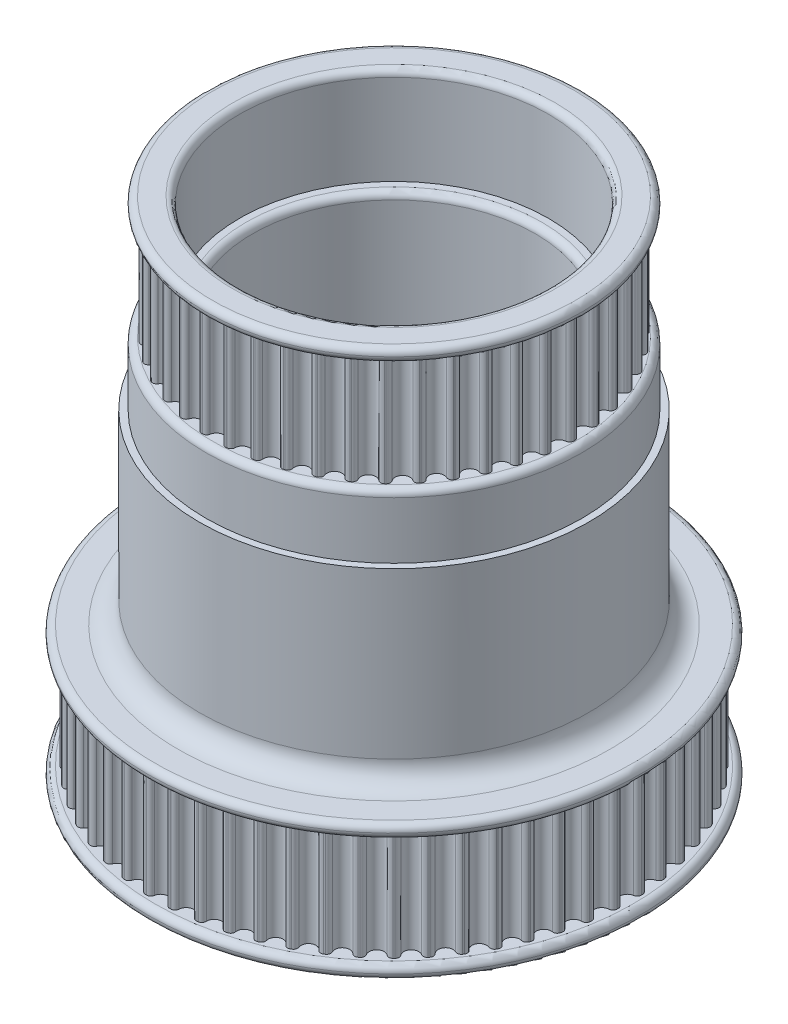
SolidWorks part; units mm, degrees
ref_plane "Front Plane" through (0, 0, 0) normal (0, 0, 1) x (1, 0, 0)
ref_plane "Top Plane" through (0, 0, 0) normal (0, 1, 0) x (1, 0, 0)
ref_plane "Right Plane" through (0, 0, 0) normal (1, 0, 0) x (0, 0, -1)
sketch "PulleyOffsets" plane through (0, 0, 0) normal (1, 0, 0) x (0, 0, -1)
  line L0 (22.225, 0) -> (-22.225, 0) construction
  line L1 (22.225, 44.45) -> (-22.225, 44.45) construction
  line L2 (0, 0) -> (0, 44.45) construction
  point P7 (0, 0)
  dimension "D1" = 44.45
ref_axis "Axis1" through (0, 34.9332, 0) along (0, -1, 0)
ref_plane "Big Pulley Plane" through (0, 0, 0) normal (0, 1, 0) x (1, 0, 0)
ref_plane "Small Pulley Plane" through (0, 44.45, 0) normal (0, 1, 0) x (1, 0, 0)
sketch "Sketch1" plane through (0, 0, 0) normal (0, 1, 0) x (1, 0, 0)
  line L0 (0, 0) -> (0, 28.2667) construction
  line L1 (0, 0) -> (2.9202, 27.7837) construction
  circle A0 centre (0, 0) radius 28.2667 construction
  circle A1 centre (0, 0) radius 27.0467 construction
  circle A2 centre (0, 27.9367) radius 0.89 construction
  circle A5 centre (2.9202, 27.7837) radius 0.89 construction
  arc A6 (0, 27.0467) -> (0.8804, 27.8061) centre (0, 27.9367) ccw
  arc A7 (0.8804, 27.8061) -> (1.3997, 28.2321) centre (1.3749, 27.7327) cw
  arc A8 (1.559, 28.2237) -> (2.031, 27.7458) centre (1.5314, 27.7245) cw
  arc A9 (2.8272, 26.8986) -> (2.031, 27.7458) centre (2.9202, 27.7837) cw
  arc A10 (1.3997, 28.2321) -> (1.559, 28.2237) centre (0, 0) cw
  arc A11 (0, 27.0467) -> (2.8272, 26.8986) centre (0, 0) ccw
  dimension "D1" = 56.5335
  dimension "D3" = 1.78
  dimension "D4" = 0.5
  dimension "D2" = 1.22
  dimension "D5" = 6
extrude "Boss-Extrude1" add sketch "Sketch1" along normal mid plane 13 contours A6 A11 A9 A8 A7 region at (0.001, 0, -0.0192)
pattern_circular "CirPattern1" count 60 over 360 about axis through (0, 34.9332, 0) along (0, -1, 0) of "Boss-Extrude1"
sketch "Sketch2" plane through (0, 0, 0) normal (1, 0, 0) x (0, 0, -1)
  line L10 (0, 6.5) -> (29.4415, 6.5) construction
  line L11 (0, 6.5) -> (0, 8.0875) construction
  line L12 (0, 8.0875) -> (29.4415, 8.0875) construction
  line L15 (29.4415, 6.5) -> (29.4415, 8.0875) construction
  line L20 (0, 34.9332) -> (0, -6.9932) construction
  line L22 (29.4415, 8.0875) -> (0, 8.0875)
  line L23 (29.4415, 8.0875) -> (29.4415, 6.5)
  line L24 (29.4415, 6.5) -> (0, 6.5)
  line L25 (0, 8.0875) -> (0, 6.5)
  dimension "D1" = 1.5875
  dimension "D2" = 29.4415
  dimension "D3" = 6.5
revolve "Revolve3" add sketch "Sketch2" angle 360 about axis through (0, 34.9332, 0) along (0, -1, 0) region at (0, 7.2937, -14.7207)
mirror "Mirror1" about plane through (0, 0, 0) normal (0, 1, 0) of "Revolve3"
sketch "Sketch6" plane through (0, 0, 0) normal (0, 1, 0) x (1, 0, 0)
  line L0 (0, 0) -> (0, 21.582) construction
  line L1 (0, 0) -> (2.8938, 21.0541) construction
  circle A0 centre (0, 0) radius 21.582 construction
  circle A1 centre (0, 0) radius 20.362 construction
  circle A2 centre (0, 21.252) radius 0.89 construction
  circle A5 centre (2.8938, 21.0541) radius 0.89 construction
  arc A6 (0, 20.362) -> (0.8793, 21.1145) centre (0, 21.252) ccw
  arc A7 (0.8793, 21.1145) -> (1.4059, 21.5362) centre (1.3733, 21.0373) cw
  arc A8 (1.5397, 21.527) -> (2.004, 21.0376) centre (1.5041, 21.0283) cw
  arc A9 (2.7726, 20.1724) -> (2.004, 21.0376) centre (2.8938, 21.0541) cw
  arc A10 (1.4059, 21.5362) -> (1.5397, 21.527) centre (0, 0) cw construction
  arc A11 (0, 20.362) -> (2.7726, 20.1724) centre (0, 0) ccw
  arc A12 (1.4059, 21.5362) -> (1.5397, 21.527) centre (0, 0) cw
  dimension "D3" = 1.78
  dimension "D4" = 0.5
  dimension "D2" = 1.22
  dimension "D1" = 43.1641
  dimension "D5" = 7.826
extrude "Boss-Extrude2" add sketch "Sketch6" along normal mid plane 13 from surface contours A6 A11 A9 A8 A7 region at (0.0017, 0, -0.025) starting at plane "Small Pulley Plane"
pattern_circular "CirPattern2" count 46 over 360 about axis through (0, 34.9332, 0) along (0, -1, 0) of "Boss-Extrude2"
sketch "Sketch9" plane through (0, 0, 0) normal (1, 0, 0) x (0, 0, -1)
  line L1 (0, 37.95) -> (22.7568, 37.95)
  line L2 (0, 37.95) -> (0, 36.3625)
  line L3 (0, 36.3625) -> (22.7568, 36.3625)
  line L4 (22.7568, 37.95) -> (22.7568, 36.3625)
  line L6 (0, 50.95) -> (22.7568, 50.95)
  line L7 (0, 50.95) -> (0, 52.5375)
  line L8 (0, 52.5375) -> (22.7568, 52.5375)
  line L9 (22.7568, 50.95) -> (22.7568, 52.5375)
  line L10 (29.4415, 8.0875) -> (29.4415, 6.5) construction
  line L11 (0, 34.9332) -> (0, -6.9932) construction
  line L12 (21.1145, 50.95) -> (20.362, 50.95) construction
  line L13 (20.1641, 37.95) -> (21.0376, 37.95) construction
  dimension "D1" = 22.7568
revolve "Revolve4" add sketch "Sketch9" angle 360 about axis through (0, 34.9332, 0) along (0, -1, 0)
sketch "Sketch10" plane through (0, -8.0875, 0) normal (0, -1, 0) x (1, 0, 0)
  circle A0 centre (0, 0) radius 18.5
  dimension "D1" = 37
extrude "Cut-Extrude1" cut sketch "Sketch10" against normal through all
sketch "Sketch11" plane through (0, 52.5375, 0) normal (0, 1, 0) x (1, 0, 0)
  circle A0 centre (0, 0) radius 22.5
  dimension "D1" = 45
extrude "Cut-Extrude2" cut sketch "Sketch11" against normal up to surface (16.175 mm away) flip side to cut up to face at (0, 36.3625, 18.5)
sketch "Sketch12" plane through (0, 0, 0) normal (0, 0, 1) x (1, 0, 0)
  line L0 (29.4415, 8.0875) -> (-29.4415, 8.0875) construction
  line L1 (18.5, 36.3625) -> (22.5, 36.3625)
  line L2 (18.5, 36.3625) -> (18.5, 8.0875) construction
  line L3 (18.5, 8.0875) -> (22.5, 8.0875)
  line L4 (22.5, 36.3625) -> (22.5, 8.0875) construction
  line L5 (22.5, 36.3625) -> (22.5, 37.95) construction
  line L6 (22.5, 30.3625) -> (22.5, 36.3625)
  line L7 (22.5, 30.3625) -> (23.2938, 30.3625)
  line L8 (22.5, 30.3625) -> (22.5, 8.0875) construction
  line L9 (22.5, 8.0875) -> (23.2938, 8.0875)
  line L10 (23.2938, 30.3625) -> (23.2938, 8.0875)
  line L11 (18.5, -8.0875) -> (18.5, 8.0875) construction
  line L12 (18.5, 2.0875) -> (16.9125, 2.0875)
  line L13 (18.5, 2.0875) -> (18.5, 40.95) construction
  line L14 (18.5, 40.95) -> (16.9125, 40.95)
  line L15 (16.9125, 2.0875) -> (16.9125, 40.95)
  line L16 (-29.4415, -8.0875) -> (29.4415, -8.0875) construction
  line L18 (18.5, 2.0875) -> (18.5, 8.0875)
  line L19 (18.5, 36.3625) -> (18.5, 40.95)
  line L20 (32.3856, 44.45) -> (-32.3856, 44.45) construction
  dimension "D1" = 6
  dimension "D2" = 0.7937
  dimension "D3" = 10.175
  dimension "D5" = 1.5875
  dimension "D4" = 3.5
revolve "Revolve5" add sketch "Sketch12" angle 360 about axis through (0, 34.9332, 0) along (0, -1, 0)
fillet "Fillet1" radius 2.54 1 edges at (0, 8.0875, -23.2938)
fillet "Fillet2" radius 0.7937 11 edges at (0, 40.95, 16.9125) (0, 52.5375, -18.5) (0, -8.0875, -18.5) (0, 2.0875, 16.9125) (0, -8.0875, 29.4415) (0, 8.0875, 29.4415) (0, 52.5375, 22.5) (0, 50.95, 22.5) (0, 37.95, -22.5) (0, 6.5, 29.4415) (0, -6.5, 29.4415)
equation "\"TEETH_NUM\"= 60"
equation "\"TOOTH_PITCH\"= 3mm"
equation "\"PITCH_LINE_OFFSET\"= .015in"
equation "\"DIAMETER_PER_GROOVE\"= \"OUTSIDE_DIAMETER\" / \"TEETH_NUM\" * 1in"
equation "\"PITCH_DIAMETER\"= ( ( \"TEETH_NUM\" * 3 - 1.31 ) / 3.1415 + .415 ) * 1mm"
equation "\"OUTSIDE_DIAMETER\"= \"PITCH_DIAMETER\" - \"PITCH_LINE_OFFSET\" * 2"
equation "\"D1@Sketch1\"=\"OUTSIDE_DIAMETER\""
equation "\"TOOTH_HEIGHT\"= 1.22mm"
equation "\"D2@Sketch1\"=\"TOOTH_HEIGHT\""
equation "\"TOOTH_DIAMETER\"= 1.78mm"
equation "\"INTERNAL_RADIUS\"= .5mm"
equation "\"D3@Sketch1\"=\"TOOTH_DIAMETER\""
equation "\"D5@Sketch1\"=360 / \"TEETH_NUM\""
equation "\"D4@Sketch1\"=\"INTERNAL_RADIUS\""
equation "\"D1@CirPattern1\"=\"TEETH_NUM\""
equation "\"BELT_GAP\"= 13mm"
equation "\"D2@Sketch2\"=\"PITCH_DIAMETER\"/2+1/32"
equation "\"D3@Sketch2\"=\"BELT_GAP\"/2"
equation "\"2_TEETH_NUM\"= 46"
equation "\"2_PITCH_DIAMETER\"= ( ( \"2_TEETH_NUM\" * 3 - 1.31 ) / 3.1415 + .415 ) * 1mm"
equation "\"2_OUTSIDE_DIAMETER\"= \"2_PITCH_DIAMETER\" - \"PITCH_LINE_OFFSET\" * 2"
equation "\"2_DIAMETER_PER_GROOVE\"= \"2_OUTSIDE_DIAMETER\" / \"2_TEETH_NUM\" * 1in"
equation "\"D5@Sketch6\"=360/\"2_TEETH_NUM\""
equation "\"D1@Sketch6\"=\"2_OUTSIDE_DIAMETER\""
equation "\"D2@Sketch6\"=\"TOOTH_HEIGHT\""
equation "\"D3@Sketch6\"=\"TOOTH_DIAMETER\""
equation "\"D4@Sketch6\"=\"INTERNAL_RADIUS\""
equation "\"2_BELT_GAP\"= 13mm"
equation "\"D1@CirPattern2\"=\"2_TEETH_NUM\""
equation "\"D1@Boss-Extrude2\"=\"2_BELT_GAP\""
equation "\"Pulley_OffSets\"= 1.75"
equation "\"D1@PulleyOffsets\" = \"Pulley_OffSets\""
equation "\"D1@Boss-Extrude1\"=\"BELT_GAP\""
equation "\"D1@Sketch9\"=\"2_PITCH_DIAMETER\"/2+1/32"
equation "\"bearing_hole_depth_arm_side\"= 7mm + .125in"
equation "\"D3@Sketch12\"=\"bearing_hole_depth_arm_side\""
